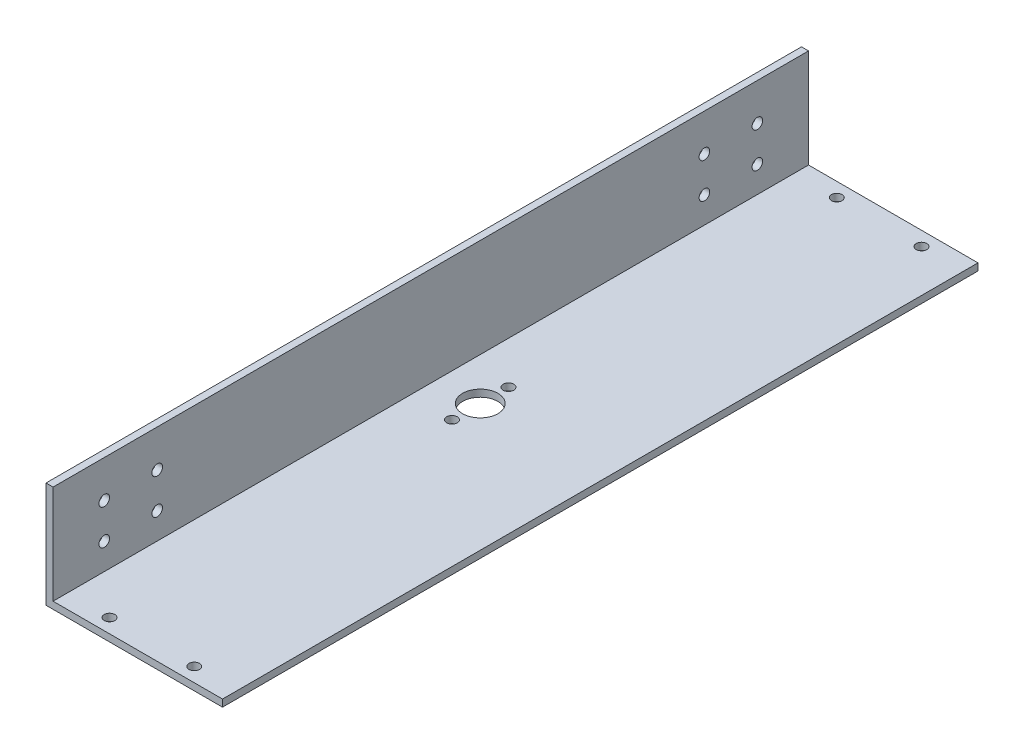
SolidWorks part; units mm, degrees
ref_plane "Front Plane" through (0, 0, 0) normal (0, 0, 1) x (1, 0, 0)
ref_plane "Top Plane" through (0, 0, 0) normal (0, 1, 0) x (1, 0, 0)
ref_plane "Right Plane" through (0, 0, 0) normal (1, 0, 0) x (0, 0, -1)
sketch "Sketch1" plane through (0, 0, 0) normal (0, 0, 1) x (1, 0, 0)
  line L0 (0, 0) -> (0, 30)
  line L1 (0, 30) -> (2, 30)
  line L2 (2, 30) -> (2, 2)
  line L3 (2, 2) -> (50, 2)
  line L4 (50, 2) -> (50, 0)
  line L5 (50, 0) -> (0, 0)
extrude "Boss-Extrude1" add sketch "Sketch1" along normal up to surface (214 mm away)
sketch "Sketch2" plane through (0, 0, 0) normal (0, -1, 0) x (1, 0, 0)
  circle A0 centre (14, 105) radius 5
extrude "Cut-Extrude1" cut sketch "Sketch2" against normal through all
sketch "Sketch4" plane through (0, 0, 0) normal (0, -1, 0) x (-1, 0, 0)
  circle A0 centre (-14, -113) radius 1.5
  circle A1 centre (-14, -97) radius 1.5
extrude "Cut-Extrude3" cut sketch "Sketch4" against normal through all
sketch "Sketch6" plane through (2, 0, 0) normal (1, 0, 0) x (0, 0, -1)
  circle A0 centre (-199.5, 9.45) radius 1.5
  circle A1 centre (-199.5, 19.45) radius 1.5
  circle A2 centre (-184.5, 9.45) radius 1.5
  circle A3 centre (-184.5, 19.45) radius 1.5
hole_wizard "Ø3.0 (3) Diameter Hole1" positions "Sketch7" profile "Sketch8" hole size "Ø3.0" standard "ISO" end condition through all
sketch "Sketch7" plane through (2, 0, 0) normal (1, 0, 0) x (0, 0, -1)
  point P0 (-199.5, 9.45)
  point P3 (-199.5, 19.45)
  point P6 (-184.5, 19.45)
  point P9 (-184.5, 9.45)
  point P12 (-29.5, 19.45)
  point P15 (-29.5, 9.45)
  point P18 (-14.5, 9.45)
  point P21 (-14.5, 19.45)
sketch "Sketch8" plane through (2, 9.45, 199.5) normal (0, 1, 0) x (0, 0, -1)
  line L0 (0, 0) -> (0, 2)
  line L1 (0, 2) -> (1.5, 2)
  line L2 (1.5, 2) -> (1.5, 0)
  line L5 (1.5, 0) -> (0, 0)
  line L11 (0, -6.35) -> (0, 107.95) construction
  dimension "Thru Hole Dia." = 3
  dimension "Thru Hole Depth" = 2
hole_wizard "Ø3.0 (3) Diameter Hole2" positions "Sketch11" profile "Sketch12" hole size "Ø3.0" standard "ISO" end condition through all
sketch "Sketch11" plane through (-23.4076, 2, 151.138) normal (0, 1, 0) x (0, 0, 1)
  point P0 (58.862, 61.4076)
  point P1 (58.862, 37.4076)
sketch "Sketch12" plane through (38, 2, 210) normal (1, 0, 0) x (0, 0, 1)
  line L0 (0, 0) -> (0, 2)
  line L1 (0, 2) -> (1.5, 2)
  line L2 (1.5, 2) -> (1.5, 0)
  line L5 (1.5, 0) -> (0, 0)
  line L11 (0, -6.35) -> (0, 107.95) construction
  dimension "Thru Hole Dia." = 3
  dimension "Thru Hole Depth" = 2
hole_wizard "Ø3.0 (3) Diameter Hole3" positions "Sketch13" profile "Sketch14" hole size "Ø3.0" standard "ISO"
sketch "Sketch13" plane through (-23.4076, 2, 151.138) normal (0, 1, 0) x (0, 0, 1)
  point P0 (-147.138, 37.4076)
  point P1 (-147.138, 61.4076)
sketch "Sketch14" plane through (14, 2, 4) normal (1, 0, 0) x (0, 0, 1)
  line L0 (0, 0) -> (0, 1.999)
  line L1 (0, 1.999) -> (1.5, 1.999)
  line L2 (1.5, 1.999) -> (1.5, 0)
  line L3 (1.5, 0) -> (0, 0)
  line L4 (0, -6.35) -> (0, 107.95) construction
  dimension "Thru Hole Dia." = 3
  dimension "Thru Hole Depth" = 1.999
